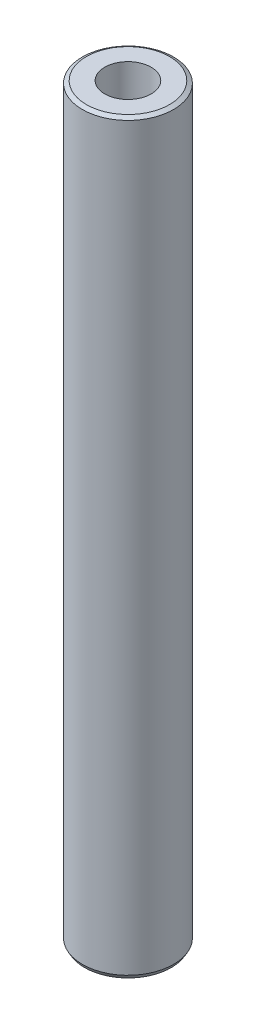
SolidWorks part; units mm, degrees
ref_plane "Front Plane" through (0, 0, 0) normal (0, 0, 1) x (1, 0, 0)
ref_plane "Top Plane" through (0, 0, 0) normal (0, 1, 0) x (1, 0, 0)
ref_plane "Right Plane" through (0, 0, 0) normal (1, 0, 0) x (0, 0, -1)
sketch "Sketch1" plane through (0, 0, 0) normal (0, 1, 0) x (1, 0, 0)
  circle A0 centre (0, 0) radius 10
  dimension "SHAFT_OD" = 20
extrude "Boss-Extrude1" add sketch "Sketch1" along normal blind 163.7721
sketch "Sketch2" plane through (0, 0, 0) normal (0, 1, 0) x (1, 0, 0)
  circle A0 centre (0, 0) radius 5.0916
  dimension "BORE_D" = 10.1833
extrude "Cut-Extrude1" cut sketch "Sketch2" along normal through all
chamfer "Chamfer1" distance 0.5045 angle 60 2 edges at (0, 163.7721, 10) (0, 0, 10) first distance on face at (0, 163.7721, 10) first distance on face at (0, 0, 5.0916)
